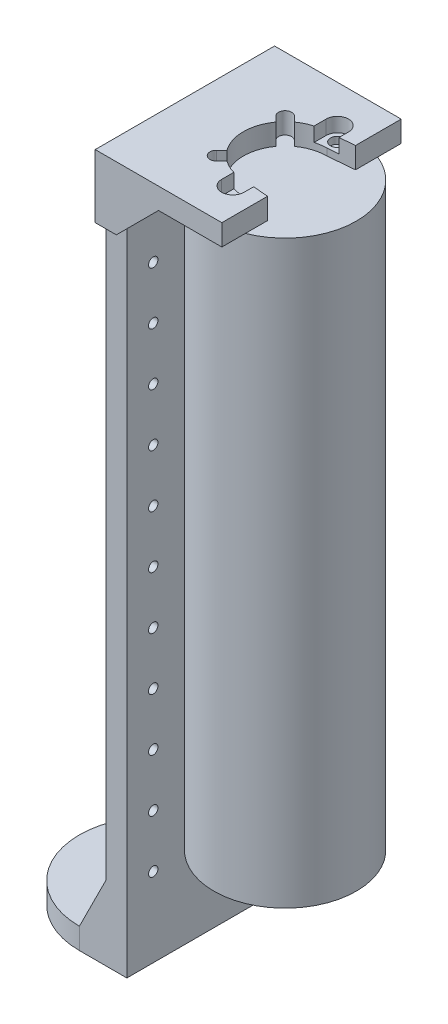
SolidWorks part; units mm, degrees
ref_plane "Front Plane" through (0, 0, 0) normal (0, 0, 1) x (1, 0, 0)
ref_plane "Top Plane" through (0, 0, 0) normal (0, 1, 0) x (1, 0, 0)
ref_plane "Right Plane" through (0, 0, 0) normal (1, 0, 0) x (0, 0, -1)
sketch "Sketch1" plane through (0, 0, 0) normal (0, 0, 1) x (1, 0, 0)
  line L0 (0, 0) -> (0, 131)
  line L1 (0, 131) -> (24, 131)
  line L2 (24, 131) -> (24, 127)
  line L3 (24, 127) -> (4, 127)
  line L4 (4, 127) -> (4, -4)
  line L5 (4, -4) -> (-20, -4)
  line L6 (-20, -4) -> (-20, 0)
  line L7 (-20, 0) -> (0, 0)
  dimension "D1" = 24
  dimension "D2" = 24
  dimension "D3" = 20
  dimension "D4" = 4
  dimension "D5" = 4
  dimension "D6" = 131
  dimension "D7" = 131
extrude "BracketMainBody" add sketch "Sketch1" along normal mid plane 30
sketch "M4_thruHole" plane through (0, -4, 0) normal (0, -1, 0) x (1, 0, 0)
  line L0 (-20, 15) -> (-20, -15) construction
  circle A0 centre (-10, 0) radius 2.4
  dimension "D1" = 4.8
  dimension "D2" = 10
  dimension "D3" = 10
sketch "SQUIDcutouts" plane through (0, 0, 0) normal (0, 1, 0) x (1, 0, 0)
  line L0 (24, -15) -> (24, 15) construction
  line L3 (0, -15) -> (0, 15) construction
  line L4 (24, 0) -> (4, 0) construction
  line L5 (12.6003, 4.6319) -> (11.6161, 5.6161)
  line L6 (13.3839, 7.3839) -> (14.3681, 6.3997)
  line L7 (11.6161, -5.6161) -> (12.6003, -4.6319)
  line L9 (13.3839, -7.3839) -> (14.3681, -6.3997)
  circle A0 centre (19, -9.9) radius 1.3
  circle A1 centre (19, 9.9) radius 1.3
  arc A2 (12.6003, 4.6319) -> (12.6003, -4.6319) centre (19, 0) ccw
  arc A3 (13.3839, 7.3839) -> (11.6161, 5.6161) centre (12.5, 6.5) ccw
  arc A4 (11.6161, -5.6161) -> (13.3839, -7.3839) centre (12.5, -6.5) ccw
  arc A5 (14.3681, -6.3997) -> (14.3681, 6.3997) centre (19, 0) ccw
  dimension "D1" = 5
  dimension "D3" = 2.6
  dimension "D4" = 2.6
  dimension "D9" = 15.8
  dimension "D12" = 2.5
  dimension "D15" = 2.5
  dimension "D18" = 1.3919
  dimension "D2" = 9.9
  dimension "D5" = 5
  dimension "D6" = 9.9
  dimension "D7" = 5
  dimension "D10" = 6.5
  dimension "D11" = 12.5
  dimension "D13" = 6.5
  dimension "D14" = 12.5
  dimension "D16" = 1.3919
  dimension "D17" = 1.3919
  dimension "D19" = 7.9424
extrude "CutExtrude_SQUIDcutouts" cut sketch "SQUIDcutouts" against normal through all from surface contours A0 | A1 | A5 L6 A3 L5 A2 L7 A4 L9 starting at face at (12, 131, 0)
sketch "champhers" plane through (0, 131, 0) normal (0, 1, 0) x (1, 0, 0)
  line L0 (24, 8.3374) -> (24, 6.1164)
  line L1 (24, 6.1164) -> (24, 15) construction
  line L2 (24, 8.3374) -> (19, 7.9)
  line L4 (30.1328, 0) -> (13.0253, 0) construction
  line L5 (24, -6.1164) -> (19, -7.9)
  line L6 (24, -8.3374) -> (19, -7.9)
  line L7 (24, -8.3374) -> (24, -6.1164)
  line L9 (19, 7.9) -> (24, 6.1164)
  arc A0 (14.3681, -6.3997) -> (14.3681, 6.3997) centre (19, 0) ccw construction
  dimension "D2" = 85
extrude "Cut-Extrude7" [suppressed] cut sketch "champhers" against normal through all
sketch "Sketch13" plane through (0, 131, 0) normal (0, 1, 0) x (1, 0, 0)
  line L0 (19, 9.9) -> (19, -9.9) construction
  line L5 (21.1241, 9.9) -> (21.1241, -9.9)
  line L6 (16.8759, 9.9) -> (16.8759, -9.9)
  arc A3 (21.1241, 9.9) -> (16.8759, 9.9) centre (19, 9.9) ccw
  arc A4 (16.8759, -9.9) -> (21.1241, -9.9) centre (19, -9.9) ccw
  point P3 (19, 0)
  dimension "D1" = 19.8
  dimension "D2" = 2.1241
ref_plane "M2CounterBore_offsetTopPlane" through (0, 128.3, 0) normal (0, 1, 0) x (1, 0, 0)
hole_wizard "M4 Clearance Hole1" positions "3DSketch1" profile "Sketch18" hole size "M4" standard "ANSI Metric" end condition up to next
sketch3d "3DSketch1"
  point P0 (-10, -4, 0)
sketch "Sketch18" plane through (-10, -4, 0) normal (1, 0, 0) x (0, 0, -1)
  line L0 (0, 0) -> (0, 4)
  line L1 (0, 4) -> (2.25, 4)
  line L2 (2.25, 4) -> (2.25, 0)
  line L5 (2.25, 0) -> (0, 0)
  line L11 (0, -6.35) -> (0, 107.95) construction
  dimension "Thru Hole Dia." = 4.5
  dimension "Thru Hole Depth" = 4
extrude "Cut-Extrude12" cut sketch "champhers<2>" against normal up to next
sketch "champhers<2>" plane through (0, 131, 0) normal (0, 1, 0) x (1, 0, 0) same geometry as "champhers"
fillet "Fillet11" radius 15 1 edges at (-20, -2, -15)
fillet "Fillet12" radius 15 1 edges at (-20, -2, 15)
fillet "Fillet13" [suppressed] radius 7.54
sketch "Sketch24" plane through (0, 0, 0) normal (1, 0, 0) x (0, 0, -1)
  line L0 (0, 0) -> (0, 131) construction
  line L1 (-15, 131) -> (15, 131) construction
  point P0 (10, 121)
  dimension "D1" = 10
  dimension "D2" = 10
hole_wizard "#2-56 Tapped Hole1" positions "3DSketch5" profile "Sketch25" tap size "#2-56" standard "ANSI Inch" end condition up to next
sketch3d "3DSketch5"
  line L0 (0, 0, 0) -> (0, 131, 0) construction
  line L1 (0, 131, 15) -> (0, 131, -15) construction
  point P4 (0, 121, -10)
  dimension "D1" = 10
  dimension "D2" = 10
sketch "Sketch25" plane through (0, 121, -10) normal (0, 1, 0) x (0, 0, 1)
  line L0 (0, 0) -> (0, 4.001)
  line L1 (0, 4.001) -> (0.889, 4.001)
  line L2 (0.889, 4.001) -> (0.889, 0)
  line L5 (0.889, 0) -> (0, 0)
  line L11 (0, -6.35) -> (0, 107.95) construction
  dimension "Thru Tap Drill Dia." = 1.778
  dimension "Thru Tap Drill Depth" = 4.001
cosmetic thread "Hole Thread2" parameters "D2"=2.1844
pattern_linear "LPattern3" count 12 spacing 10 along (0, -1, 0) count 2 spacing 20 along (0, 0, 1) of "#2-56 Tapped Hole1"
cosmetic thread "Hole Thread3" parameters "D2"=2.1844
cosmetic thread "Hole Thread4" parameters "D2"=2.1844
cosmetic thread "Hole Thread5" parameters "D2"=2.1844
cosmetic thread "Hole Thread6" parameters "D2"=2.1844
cosmetic thread "Hole Thread7" parameters "D2"=2.1844
cosmetic thread "Hole Thread8" parameters "D2"=2.1844
cosmetic thread "Hole Thread9" parameters "D2"=2.1844
cosmetic thread "Hole Thread10" parameters "D2"=2.1844
cosmetic thread "Hole Thread11" parameters "D2"=2.1844
cosmetic thread "Hole Thread12" parameters "D2"=2.1844
cosmetic thread "Hole Thread13" parameters "D2"=2.1844
cosmetic thread "Hole Thread14" parameters "D2"=2.1844
cosmetic thread "Hole Thread15" parameters "D2"=2.1844
cosmetic thread "Hole Thread16" parameters "D2"=2.1844
cosmetic thread "Hole Thread17" parameters "D2"=2.1844
cosmetic thread "Hole Thread18" parameters "D2"=2.1844
cosmetic thread "Hole Thread19" parameters "D2"=2.1844
cosmetic thread "Hole Thread20" parameters "D2"=2.1844
cosmetic thread "Hole Thread21" parameters "D2"=2.1844
cosmetic thread "Hole Thread22" parameters "D2"=2.1844
cosmetic thread "Hole Thread23" parameters "D2"=2.1844
cosmetic thread "Hole Thread24" parameters "D2"=2.1844
cosmetic thread "Hole Thread25" parameters "D2"=2.1844
extrude "Cut-Extrude14" cut sketch "Sketch13" against normal up to surface (2.7 mm away) contours L5 A4 L6 A3 up to plane "M2CounterBore_offsetTopPlane"
sketch "Sketch28" plane through (0, 0, -15) normal (0, 0, -1) x (-1, 0, 0)
  line L0 (-24, 131) -> (-24, 127)
  line L1 (-24, 131) -> (0, 131)
  line L2 (0, 131) -> (0, 119)
  line L3 (0, 131) -> (0, 0) construction
  line L4 (0, 119) -> (-4, 119)
  line L5 (-4, -4) -> (-4, 127) construction
  line L7 (-4, 127) -> (-24, 127) construction
  line L8 (-12, 127) -> (-4, 119)
  line L9 (-24, 127) -> (-12, 127)
  dimension "D1" = 12
  dimension "D2" = 24
  dimension "D3" = 4
  dimension "D4" = 12
extrude "Boss-Extrude1" add sketch "Sketch28" along normal blind 2
sketch "Sketch29" plane through (0, 0, 15) normal (0, 0, 1) x (1, 0, 0)
  line L0 (24, 131) -> (0, 131)
  line L1 (24, 131) -> (0, 131) construction
  line L2 (0, 131) -> (0, 119)
  line L3 (0, 131) -> (0, 0) construction
  line L4 (0, 119) -> (4, 119)
  line L5 (4, -4) -> (4, 127) construction
  line L7 (4, 127) -> (24, 127) construction
  line L8 (12, 127) -> (4, 119)
  line L9 (24, 131) -> (24, 127)
  line L10 (24, 127) -> (12, 127)
  dimension "D1" = 24
  dimension "D2" = 12
  dimension "D3" = 4
  dimension "D4" = 12
extrude "Boss-Extrude2" add sketch "Sketch29" along normal blind 2
fillet "Fillet15" radius 3.5 1 edges at (8, 127, 15)
fillet "Fillet16" radius 3.5 1 edges at (8, 127, -15)
sketch "Sketch30" plane through (0, 0, 15) normal (0, 0, 1) x (1, 0, 0)
  line L0 (-5, 0) -> (0, 0)
  line L1 (-20, 0) -> (0, 0) construction
  line L2 (0, 0) -> (0, 10)
  line L3 (0, 0) -> (0, 131) construction
  line L4 (0, 10) -> (-5, 0)
  dimension "D1" = 10
  dimension "D2" = 5
extrude "Boss-Extrude3" add sketch "Sketch30" against normal blind 2
sketch "Sketch31" plane through (0, 0, -15) normal (0, 0, -1) x (-1, 0, 0)
  line L0 (0, 10) -> (0, 0)
  line L1 (0, 119) -> (0, 0) construction
  line L2 (0, 0) -> (5, 0)
  line L3 (0, 0) -> (5, 0) construction
  line L4 (5, 0) -> (0, 10)
  dimension "D1" = 10
  dimension "D2" = 5
extrude "Boss-Extrude4" add sketch "Sketch31" against normal blind 2
fillet "Fillet17" radius 3.5 1 edges at (-2.5, 0, -13)
fillet "Fillet18" radius 3.5 1 edges at (-2.5, 0, 13)
sketch "Sketch32" plane through (0, 127, 0) normal (0, -1, 0) x (1, 0, 0)
  circle A0 centre (19, 0) radius 13.5
  point P2 (19, 0)
  dimension "D1" = 27
extrude "Boss-Extrude5" add sketch "Sketch32" along normal blind 110
